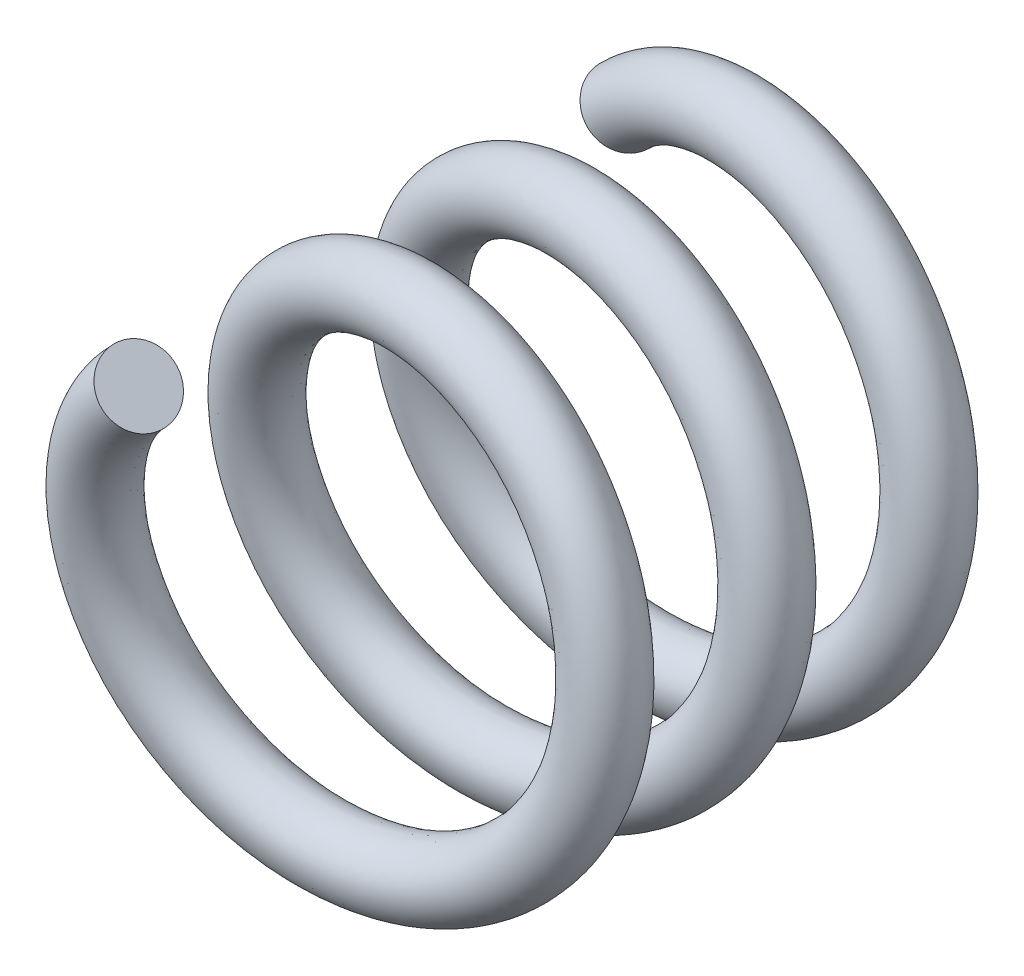
SolidWorks part; units mm, degrees
ref_plane "Front Plane" through (0, 0, 0) normal (0, 0, 1) x (1, 0, 0)
ref_plane "Top Plane" through (0, 0, 0) normal (0, 1, 0) x (1, 0, 0)
ref_plane "Right Plane" through (0, 0, 0) normal (1, 0, 0) x (0, 0, -1)
sketch "Sketch1" plane through (0, 0, 0) normal (0, 0, 1) x (1, 0, 0)
  circle A0 centre (0, 0) radius 3.065
  dimension "D1" = 6.13
curve "Helix/Spiral1" pitch 2.3333 height 7 radius 3.065 left hand yes centre (0, 0, 0) axis (0, 0, 1) start towards (-0.7071, 0.7071, 0)
ref_plane "Plane2" through (-2.1673, 2.1673, 0) normal (0.702, 0.702, 0.1203) x (0.7122, -0.69, -0.1294)
sketch "Sketch3" plane through (-2.1673, 2.1673, 0) normal (0.702, 0.702, 0.1203) x (0.7122, -0.69, -0.1294)
  circle A0 centre (0, 0) radius 0.5
sweep "Sweep1" add profiles "Sketch3" path "Helix/Spiral1"
ref_plane "Plane3" through (0, 0, 0) normal (0, 0, 1) x (1, 0, 0)
ref_plane "Plane4" through (0, 0, 7) normal (0, 0, 1) x (1, 0, 0)
ref_plane "Plane5" through (0, 0, 7.5) normal (0, 0, 1) x (1, 0, 0)
ref_plane "Plane6" through (0, 0, -0.5) normal (0, 0, 1) x (1, 0, 0)
equation "\"spring_diameter\"=6.13"
equation "\"coil_diameter\"=1.00"
equation "\"number_of_coils\"=3"
equation "\"D1@Sketch1\"=\"spring_diameter\""
equation "\"spring_length\"=7"
equation "\"D3@Helix/Spiral1\"=\"spring_length\""
equation "\"D1@Sketch3\"=\"coil_diameter\""
equation "\"D1@Plane5\"=\"coil_diameter\"/2"
equation "\"D1@Plane6\"=\"coil_diameter\"/2"
